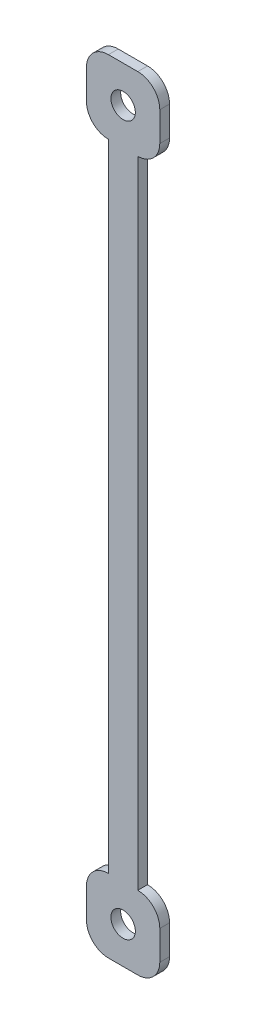
SolidWorks part; units mm, degrees
ref_plane "前视基准面" through (0, 0, 0) normal (0, 0, 1) x (1, 0, 0)
ref_plane "上视基准面" through (0, 0, 0) normal (0, 1, 0) x (1, 0, 0)
ref_plane "右视基准面" through (0, 0, 0) normal (1, 0, 0) x (0, 0, -1)
sketch "草图1" plane through (0, 0, 0) normal (0, 0, 1) x (1, 0, 0)
  line L0 (-7.5, 7.5) -> (-7.5, -7.5)
  line L1 (-7.5, 7.5) -> (7.5, 7.5)
  line L3 (-7.5, -152.5) -> (7.5, -152.5)
  line L6 (7.5, 7.5) -> (7.5, -7.5)
  line L7 (7.5, -152.5) -> (7.5, -137.5)
  line L8 (-7.5, -137.5) -> (-7.5, -152.5)
  line L10 (3, -137.5) -> (3, -7.5)
  line L11 (-3, -7.5) -> (-3, -137.5)
  line L12 (-7.5, -7.5) -> (-3, -7.5)
  line L13 (7.5, -7.5) -> (3, -7.5)
  line L14 (-7.5, -137.5) -> (-3, -137.5)
  line L15 (7.5, -137.5) -> (3, -137.5)
  circle A0 centre (0, 0) radius 2.5
  circle A1 centre (0, -145) radius 2.5
extrude "凸台-拉伸1" add sketch "草图1" along normal blind 2
fillet "圆角1" radius 4.5 8 edges at (-7.5, 7.5, 1) (-7.5, -7.5, 1) (7.5, -7.5, 1) (7.5, 7.5, 1) (7.5, -152.5, 1) (7.5, -137.5, 1) (-7.5, -152.5, 1) (-7.5, -137.5, 1)
